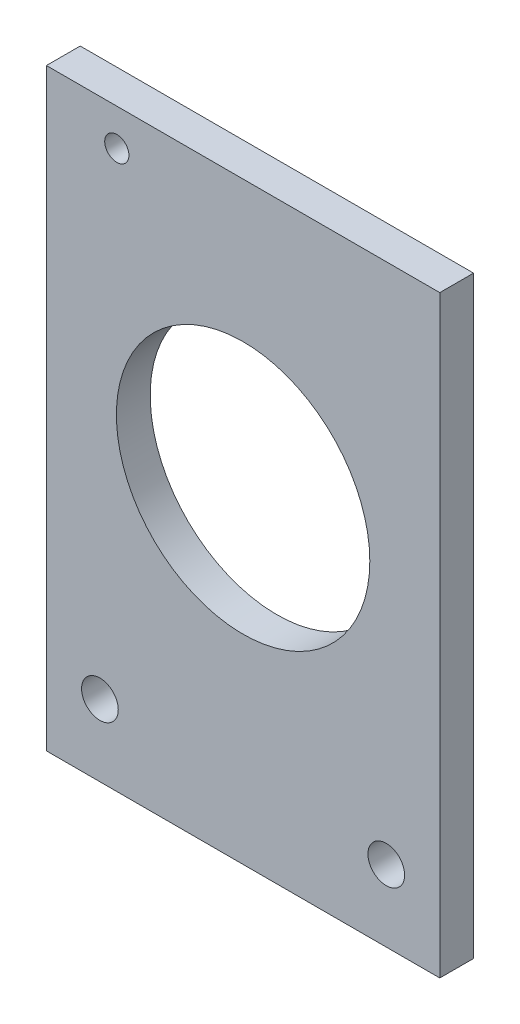
SolidWorks part; units mm, degrees
ref_plane "Front Plane" through (0, 0, 0) normal (0, 0, 1) x (1, 0, 0)
ref_plane "Top Plane" through (0, 0, 0) normal (0, 1, 0) x (1, 0, 0)
ref_plane "Right Plane" through (0, 0, 0) normal (1, 0, 0) x (0, 0, -1)
sketch "Sketch2" plane through (0, 0, 0) normal (0, 0, 1) x (1, 0, 0)
  line L0 (-55, 48.4) -> (55, 48.4) construction
  line L1 (-34.925, 0) -> (34.925, 0)
  line L2 (-34.925, 0) -> (-34.925, 57.9)
  line L3 (-34.925, 57.9) -> (34.925, 57.9) construction
  line L4 (34.925, 0) -> (34.925, 57.9)
  line L5 (0, 48.4) -> (0, 0) construction
  line L6 (0, 48.4) -> (0, 57.9) construction
  line L7 (-34.925, 25.4) -> (34.925, 25.4) construction
  line L10 (34.925, 90.4) -> (-34.925, 90.4) construction
  line L11 (34.925, 57.9) -> (34.925, 90.4)
  line L12 (34.925, 90.4) -> (-34.925, 90.4) construction
  line L13 (-34.925, 90.4) -> (-34.925, 57.9)
  line L14 (34.925, 90.4) -> (34.925, 105.4)
  line L15 (34.925, 105.4) -> (-34.925, 105.4)
  line L16 (-34.925, 90.4) -> (-34.925, 105.4)
  line L17 (-34.925, 25.4) -> (34.925, 25.4) construction
  circle A0 centre (-55, 48.4) radius 3 construction
  circle A1 centre (55, 48.4) radius 3 construction
  circle A2 centre (-55, 48.4) radius 15 construction
  circle A3 centre (55, 48.4) radius 15 construction
  circle A6 centre (0, 57.9) radius 22.5
  circle A7 centre (-55, 48.4) radius 15.6 construction
  point P6 (0, 0)
  dimension "D1" = 6
  dimension "D2" = 30
  dimension "D5" = 45
  dimension "D9" = 15
  dimension "D3" = 110
  dimension "D4" = 9.5
  dimension "D6" = 69.85
  dimension "D7" = 0.6
  dimension "D8" = 32.5
  dimension "D10" = 25.4
  dimension "D12" = 32.5
extrude "Boss-Extrude1" add sketch "Sketch2" along normal mid plane 6
sketch "Sketch3" plane through (0, 0, 3) normal (0, 0, 1) x (1, 0, 0)
  line L0 (34.925, 105.4) -> (-34.925, 105.4) construction
  line L1 (-34.925, 0) -> (-25.425, 0) construction
  line L2 (-34.925, 0) -> (-34.925, 12.7) construction
  line L3 (-34.925, 12.7) -> (-25.425, 12.7) construction
  line L4 (-25.425, 0) -> (-25.425, 12.7) construction
  line L5 (34.925, 0) -> (25.425, 0) construction
  line L6 (34.925, 0) -> (34.925, 12.7) construction
  line L7 (34.925, 12.7) -> (25.425, 12.7) construction
  line L8 (25.425, 0) -> (25.425, 12.7) construction
  line L11 (-34.925, 105.4) -> (-34.925, 0) construction
  circle A0 centre (-25.425, 12.7) radius 3.2576
  circle A1 centre (25.425, 12.7) radius 3.2576
  circle A4 centre (-22.425, 98.9) radius 2.15
  dimension "D1" = 12.7
  dimension "D2" = 6.5151
  dimension "D7" = 4.3
  dimension "D3" = 9.5
  dimension "D8" = 12.5
  dimension "D9" = 6.5
extrude "Cut-Extrude1" cut sketch "Sketch3" against normal blind 6
